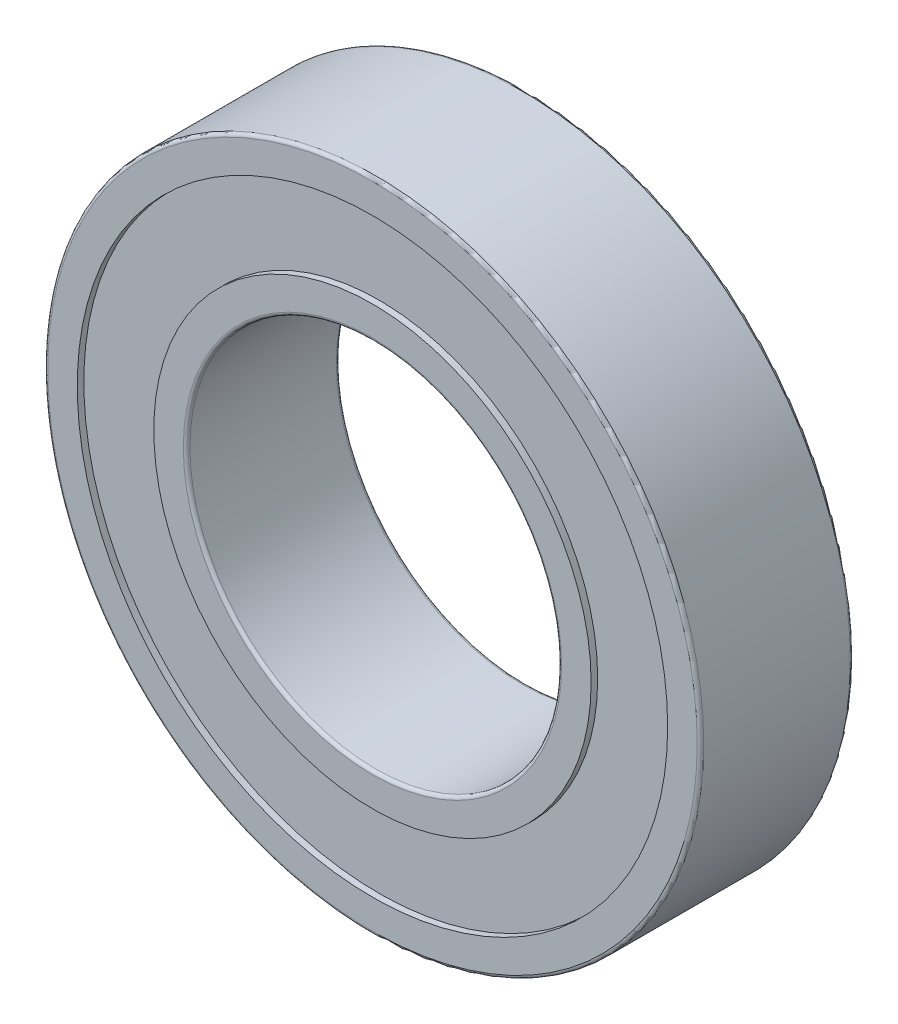
SolidWorks part; units mm, degrees
ref_plane "Front Plane" through (0, 0, 0) normal (0, 0, 1) x (1, 0, 0)
ref_plane "Top Plane" through (0, 0, 0) normal (0, 1, 0) x (1, 0, 0)
ref_plane "Right Plane" through (0, 0, 0) normal (1, 0, 0) x (0, 0, -1)
sketch "Sketch1" plane through (0, 0, 0) normal (0, 0, 1) x (1, 0, 0)
  circle A0 centre (0, 0) radius 8.5
  circle A1 centre (0, 0) radius 15
  dimension "D1" = 17
  dimension "D2" = 30
extrude "Boss-Extrude1" add sketch "Sketch1" along normal blind 7
sketch "Sketch2" plane through (0, 0, 7) normal (0, 0, 1) x (1, 0, 0)
  circle A2 centre (0, 0) radius 13.5
  circle A3 centre (0, 0) radius 13.5
  circle A5 centre (0, 0) radius 10
  circle A6 centre (0, 0) radius 10
  dimension "D1" = 1.5
  dimension "D2" = 1.5
extrude "Cut-Extrude1" cut sketch "Sketch2" against normal blind 0.3
extrude "Cut-Extrude2" cut sketch "Sketch2<2>" along normal blind 0.5 from surface starting at face at (15, 0, 0)
sketch "Sketch2<2>" plane through (0, 0, 7) normal (0, 0, 1) x (1, 0, 0) same geometry as "Sketch2"
fillet "Fillet1" radius 0.15 4 edges at (8.5, 0, 7) (15, 0, 7) (8.5, 0, 0) (15, 0, 0)
